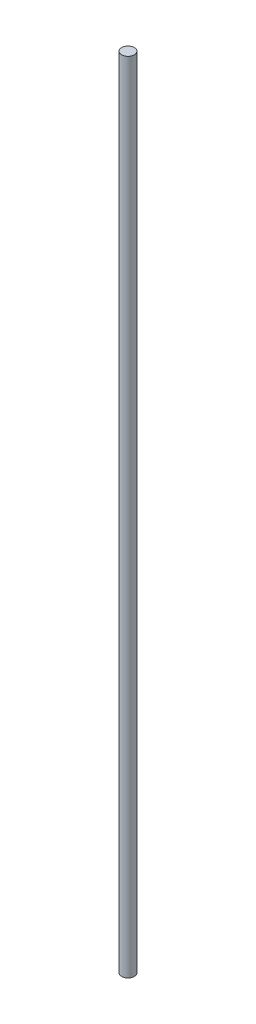
SolidWorks part; units mm, degrees
ref_plane "Front Plane" through (0, 0, 0) normal (0, 0, 1) x (1, 0, 0)
ref_plane "Top Plane" through (0, 0, 0) normal (0, 1, 0) x (1, 0, 0)
ref_plane "Right Plane" through (0, 0, 0) normal (1, 0, 0) x (0, 0, -1)
sketch "Sketch1" plane through (0, 0, 0) normal (0, 1, 0) x (1, 0, 0)
  circle A0 centre (0, 0) radius 3.175
  dimension "D1" = 6.35
extrude "Boss-Extrude1" add sketch "Sketch1" along normal blind 400
